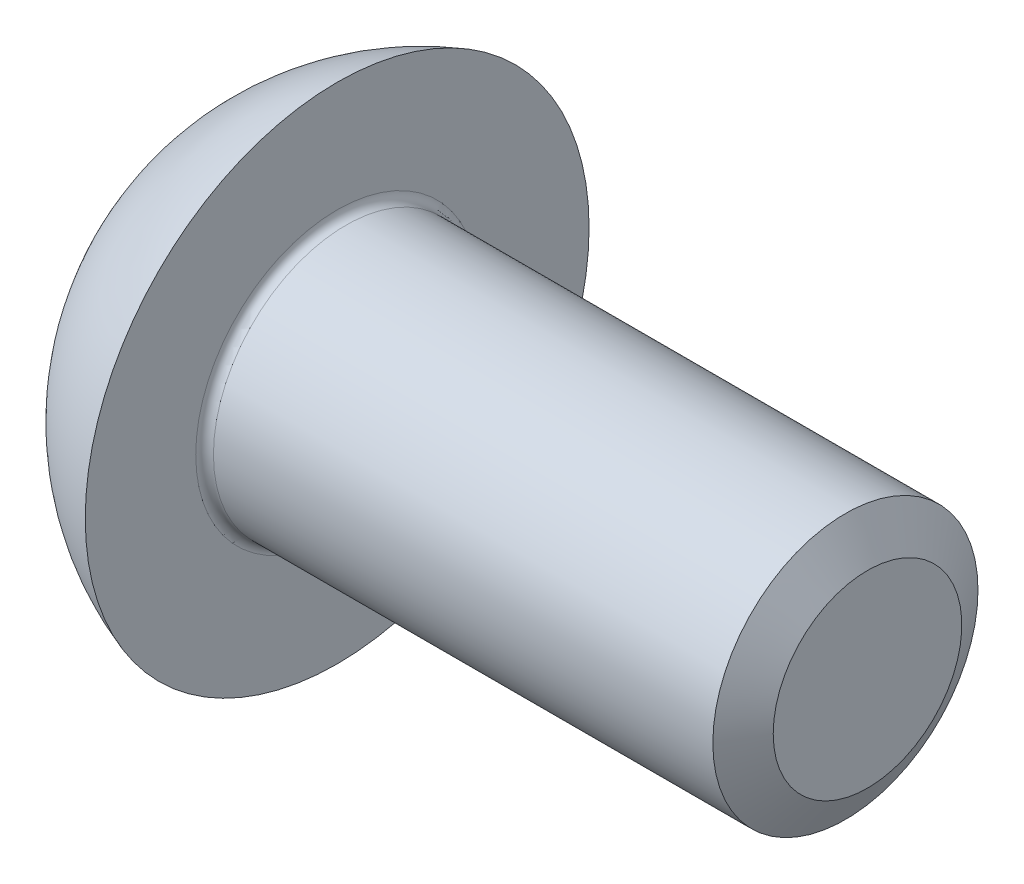
SolidWorks part; units mm, degrees
material "8.8级"
ref_plane "前视基准面" through (0, 0, 0) normal (0, 0, 1) x (1, 0, 0)
ref_plane "上视基准面" through (0, 0, 0) normal (0, 1, 0) x (1, 0, 0)
ref_plane "右视基准面" through (0, 0, 0) normal (1, 0, 0) x (0, 0, -1)
sketch "草图1" plane through (0, 0, 0) normal (0, 0, 1) x (1, 0, 0)
  line L0 (-7.65, 0) -> (0, 0) construction
  line L1 (0, 1.5) -> (-5.9, 1.5)
  line L2 (-6, 1.6) -> (-6, 2.85)
  line L3 (-7.65, 0) -> (-7.65, 1.5)
  line L4 (0, 1.5) -> (0, 0)
  line L5 (-7.65, 0) -> (0, 0)
  arc A0 (-6, 2.85) -> (-7.65, 1.5) centre (-5.0455, 0) ccw
  arc A1 (-5.9, 1.5) -> (-6, 1.6) centre (-5.9, 1.6) cw
  point P10 (-6, 1.5)
  dimension "r" = 0.1
  dimension "d" = 3
  dimension "dk" = 5.7
  dimension "k" = 1.65
  dimension "l" = 6
revolve "旋转1" add sketch "草图1" angle 360 about L0
cosmetic thread "装饰螺纹线1" parameters "D1"=2, "D2"=2.58
sketch "草图2" plane through (-7.65, 0, 0) normal (-1, 0, 0) x (0, 0, 1)
  line L1 (0, 1.1547) -> (-1, 0.5774)
  line L2 (-1, 0.5774) -> (-1, -0.5774)
  line L3 (-1, -0.5774) -> (0, -1.1547)
  line L4 (0, -1.1547) -> (1, -0.5774)
  line L5 (1, -0.5774) -> (1, 0.5774)
  line L6 (1, 0.5774) -> (0, 1.1547)
  circle A0 centre (0, 0) radius 1 construction
  dimension "s" = 2
extrude "切除-拉伸1" cut sketch "草图2" against normal blind 1.65
sketch "草图6" plane through (0, 0, 0) normal (0, 0, 1) x (1, 0, 0)
  line L0 (-6.61, 1.1547) -> (-6, 0)
  line L1 (-5.7, 1.1547) -> (-5.7, 0)
  line L2 (-5.7, 1.1547) -> (-6.61, 1.1547)
  line L3 (-7.65, 0) -> (-6, 0) construction
  line L4 (-5.7, 0) -> (-6, 0)
  line L5 (-7.65, 0) -> (-9.95, 0) construction
  dimension "t" = 1.04
  dimension "e-s" = 0.3
  dimension "k" = 1.65
  dimension "e" = 2.3
revolve "旋转2" add sketch "草图6" angle 360 about L3
sketch "草图7" plane through (0, 0, 0) normal (0, 0, 1) x (1, 0, 0)
  line L3 (-7.65, 1.1547) -> (-7.35, 0)
  line L4 (-7.65, 0) -> (-7.35, 0) construction
  line L7 (-7.65, 1.1547) -> (-7.65, 0)
  line L8 (-7.65, 0) -> (-7.35, 0)
  dimension "e-s" = 0.3
revolve "切除-旋转5" cut sketch "草图7" angle 360 about L4
sketch "草图4" plane through (0, 0, 0) normal (0, 0, 1) x (1, 0, 0)
  line L0 (-0.25, 1.5) -> (0, 1.067)
  line L1 (-0.25, 1.5) -> (0.25, 1.5)
  line L2 (0.25, 1.5) -> (0, 1.067)
  line L4 (0, -1.5) -> (0, 1.5) construction
  line L5 (-0.25, 0) -> (0.25, 0) construction
  dimension "d" = 1.5
  dimension "p" = 0.5
revolve "切除-旋转1" cut sketch "草图4" angle 360 about L5
ref_axis "基准轴1" through (-8.1887, 0, 0) along (1, 0, 0)
pattern_linear "阵列(线性)1" [suppressed] count 4 spacing 0.5 along (-1, 0, 0) of bodies 104
equation "\"D2@装饰螺纹线1\" = \"d@草图1\" * 0.86"
equation "\"k@草图6\" = \"k@切除-拉伸1\""
equation "\"e-s@草图6\" = \"e@草图6\" - \"s@草图2\""
equation "\"e-s@草图7\" = \"e-s@草图6\""
equation "\"d@草图4\" = \"d@草图1\" / 2"
equation "\"k@切除-拉伸1\" = \"k@草图1\""
equation "\"D1@阵列(线性)1\" = \"D1@装饰螺纹线1\" / \"p@草图4\""
equation "\"D3@阵列(线性)1\" = \"p@草图4\""
